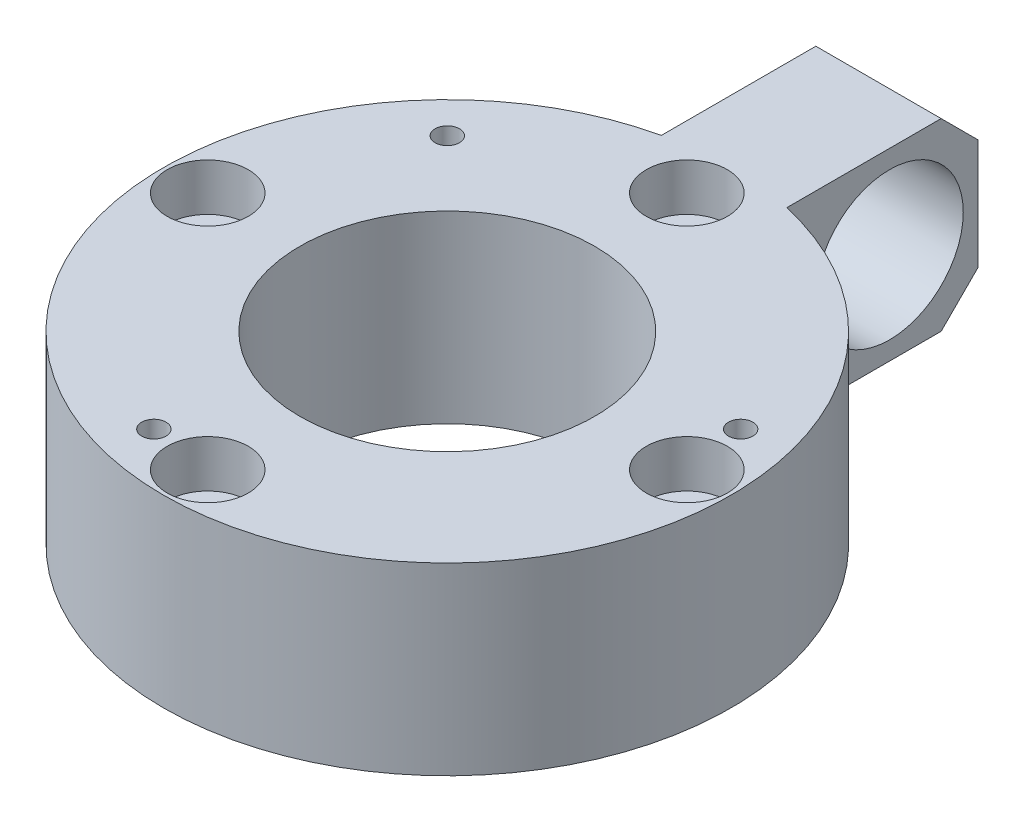
SolidWorks part; units mm, degrees
material "AISI 316 (1.4401)"
ref_plane "Płaszczyzna przednia" through (0, 0, 0) normal (0, 0, 1) x (1, 0, 0)
ref_plane "Płaszczyzna górna" through (0, 0, 0) normal (0, 1, 0) x (1, 0, 0)
ref_plane "Płaszczyzna prawa" through (0, 0, 0) normal (1, 0, 0) x (0, 0, -1)
sketch "Szkic1" plane through (0, 0, 0) normal (0, 1, 0) x (1, 0, 0)
  circle A0 centre (0, 0) radius 38.5
  circle A1 centre (0, 0) radius 20
  dimension "D1" = 77
  dimension "D2" = 40
extrude "Dodanie-wyciągnięcie1" add sketch "Szkic1" along normal blind 25
hole_wizard "Pogłębienie walcowe pod M6 Wkręt z łbem walcowym z gniazdem sześciokątnym1" positions "Szkic2" profile "Szkic3" counterbore size "M6" standard "DIN" end condition up to next
sketch "Szkic2" plane through (0, 25, 0) normal (0, 1, 0) x (1, 0, 0)
  line L0 (0, 0) -> (0, 32.5) construction
  point P0 (0, 32.5)
  dimension "D1" = 32.5
sketch "Szkic3" plane through (0, 25, -32.5) normal (1, 0, 0) x (0, 0, 1)
  line L0 (0, 0) -> (0, 25)
  line L1 (0, 25) -> (3.3, 25)
  line L3 (3.3, 25) -> (3.3, 6.4)
  line L4 (3.3, 6.4) -> (5.5, 6.4)
  line L5 (5.5, 6.4) -> (5.5, 0)
  line L7 (5.5, 0) -> (0, 0)
  line L11 (0, -6.35) -> (0, 107.95) construction
  dimension "Średnica otworu na wylot" = 6.6
  dimension "Głębokość otworu na wylot" = 25
  dimension "Średnica pogłębienia walcowego" = 11
  dimension "Głębokość pogłębienia walcowego" = 6.4
pattern_circular "Szyk kołowy1" count 4 over 360 about axis through (0, 25, 0) along (0, -1, 0) of "Pogłębienie walcowe pod M6 Wkręt z łbem walcowym z gniazdem sześciokątnym1"
sketch "Szkic4" plane through (0, 25, 0) normal (0, 1, 0) x (1, 0, 0)
  line L0 (-8.5, 37.55) -> (-8.5, 63.5)
  line L1 (-8.5, 63.5) -> (8.5, 63.5)
  line L2 (8.5, 63.5) -> (8.5, 37.55)
  circle A0 centre (0, 0) radius 38.5 construction
  circle A2 centre (0, 0) radius 38.5
  arc A3 (8.5, 37.55) -> (-8.5, 37.55) centre (0, 0) ccw
  dimension "D2" = 25
  dimension "D3" = 0
  dimension "D1" = 17
extrude "Dodanie-wyciągnięcie2" add sketch "Szkic4" against normal blind 25
hole_wizard "Otwór Ø20.0 (20)2" positions "Szkic5" profile "Szkic6" hole size "Ø8.0" standard "DIN" end condition up to next
sketch "Szkic5" plane through (-8.5, 0, 0) normal (-1, 0, 0) x (0, 0, 1)
  line L0 (-63.5, 12.5) -> (-51.5, 12.5) construction
  line L1 (-63.5, 0) -> (-63.5, 25) construction
  point P0 (-51.5, 12.5)
  dimension "D1" = 12
sketch "Szkic6" plane through (-8.5, 12.5, -51.5) normal (0, 1, 0) x (0, 0, 1)
  line L0 (0, 0) -> (0, 17)
  line L1 (0, 17) -> (10, 17)
  line L2 (10, 17) -> (10, 0)
  line L5 (10, 0) -> (0, 0)
  line L11 (0, -6.35) -> (0, 107.95) construction
  dimension "Średnica otworu na wylot" = 20
  dimension "Głębokość otworu na wylot" = 17
chamfer "Sfazowanie1" distance 5 angle 45 2 edges at (0, 0, -63.5) (0, 25, -63.5)
hole_wizard "Otwór gwintowany M41" positions "Szkic7" profile "Szkic8" tap size "M4" standard "DIN"
sketch "Szkic7" plane through (0, 25, 0) normal (0, 1, 0) x (1, 0, 0)
  line L0 (0, 0) -> (-8.4116, -31.3926) construction
  line L1 (-8.4116, -31.3926) -> (-22.981, 22.981) construction
  line L2 (-22.981, 22.981) -> (31.3926, 8.4116) construction
  line L3 (31.3926, 8.4116) -> (-8.4116, -31.3926) construction
  line L5 (-22.981, 22.981) -> (0, 0) construction
  line L6 (0, 0) -> (31.3926, 8.4116) construction
  line L8 (0, 0) -> (0, -32.5) construction
  point P0 (-8.4116, -31.3926)
  point P2 (-22.981, 22.981)
  point P4 (31.3926, 8.4116)
  dimension "D1" = 32.5
  dimension "D2" = 15
sketch "Szkic8" plane through (-8.4116, 25, 31.3926) normal (1, 0, 0) x (0, 0, 1)
  line L0 (0, 0) -> (0, 12.4914)
  line L1 (0, 12.4914) -> (1.65, 11.5)
  line L2 (1.65, 11.5) -> (1.65, 0)
  line L5 (1.65, 0) -> (0, 0)
  line L10 (0, 12.4914) -> (-1.65, 11.5) construction
  line L11 (0, -6.35) -> (0, 107.95) construction
  dimension "Średnica wiertła gwintu" = 3.3
  dimension "Głębokość otworu gwintowanego" = 11.5
  dimension "Kąt wiertła" = 118
cosmetic thread "Gwint otworu1" parameters "D1"=8, "D2"=4
cosmetic thread "Gwint otworu2" parameters "D1"=8, "D2"=4
cosmetic thread "Gwint otworu3" parameters "D1"=8, "D2"=4
